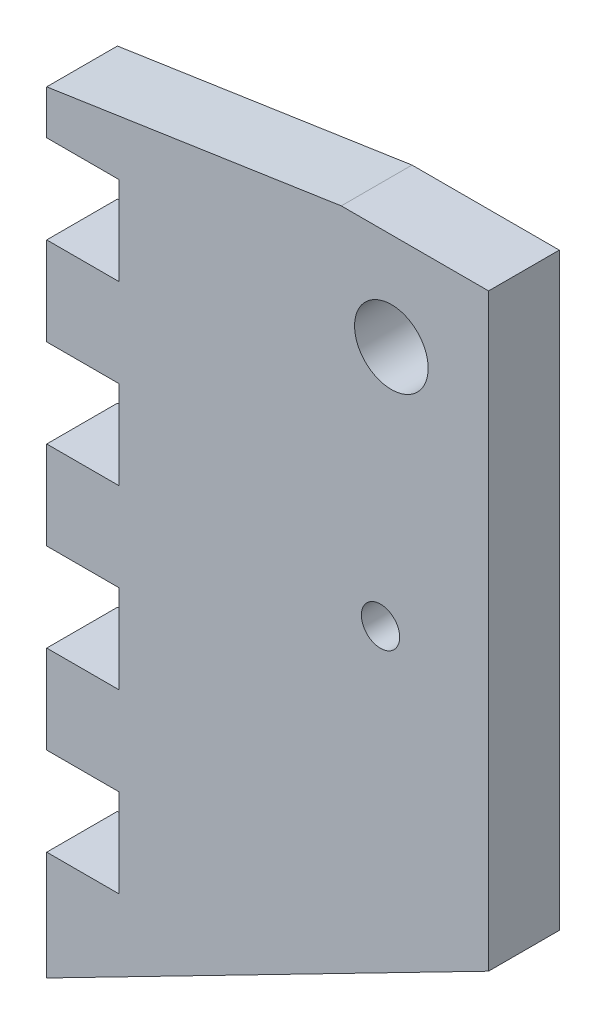
SolidWorks part; units mm, degrees
material "Thornel VCB-20 Carbon Cloth"
ref_plane "Front Plane" through (0, 0, 0) normal (0, 0, 1) x (1, 0, 0)
ref_plane "Top Plane" through (0, 0, 0) normal (0, 1, 0) x (1, 0, 0)
ref_plane "Right Plane" through (0, 0, 0) normal (1, 0, 0) x (0, 0, -1)
sketch "Sketch1" plane through (0, 0, 0) normal (0, 0, 1) x (1, 0, 0)
  line L0 (0, 0) -> (-38.1, 0)
  line L1 (0, 0) -> (0, -50.8)
  line L2 (-38.1, 0) -> (-38.1, -7.62)
  line L3 (-38.1, -7.62) -> (-31.877, -7.62)
  line L4 (-31.877, -7.62) -> (-31.877, -15.24)
  line L5 (-31.877, -15.24) -> (-38.1, -15.24)
  line L6 (-38.1, -45.72) -> (-38.1, -70.358)
  line L7 (-38.1, -15.24) -> (-38.1, -22.86)
  line L8 (-38.1, -22.86) -> (-31.877, -22.86)
  line L9 (-31.877, -22.86) -> (-31.877, -30.48)
  line L10 (-31.877, -30.48) -> (-38.1, -30.48)
  line L11 (-38.1, -30.48) -> (-38.1, -38.1)
  line L12 (-38.1, -38.1) -> (-31.877, -38.1)
  line L13 (-31.877, -38.1) -> (-31.877, -45.72)
  line L14 (-31.877, -45.72) -> (-38.1, -45.72)
  line L15 (-38.1, -70.358) -> (0, -50.8)
  circle A0 centre (-8.382, -8.382) radius 3.175
  dimension "D9" = 6.35
  dimension "D1" = 38.1
  dimension "D2" = 50.8
  dimension "D3" = 7.62
  dimension "D4" = 7.62
  dimension "D6" = 6.223
  dimension "D8" = 70.358
  dimension "D12" = 8.382
  dimension "D13" = 8.382
  dimension "D7" = 3
extrude "Boss-Extrude1" add sketch "Sketch1" along normal blind 6.096 contours L6 L15 L1 L0 L2 L3 L4 L5 L7 L8 L9 L10 L11 L12 L13 L14 A0 region at (-19.2545, -31.1404, 0)
sketch "Sketch2" plane through (0, 0, 0) normal (0, 0, -1) x (-1, 0, 0)
  line L5 (38.1, 0) -> (12.7, 0)
  line L6 (0, 0) -> (38.1, 0) construction
  line L7 (12.7, 0) -> (38.1, -3.81)
  line L8 (38.1, 0) -> (38.1, -7.62) construction
  line L9 (38.1, -3.81) -> (38.1, 0)
  dimension "D1" = 25.4
  dimension "D2" = 3.81
extrude "Cut-Extrude1" cut sketch "Sketch2" against normal blind 8.636
sketch "Sketch4" plane through (0, 0, 6.096) normal (0, 0, 1) x (1, 0, 0)
  line L0 (-38.1, -45.72) -> (-38.1, -53.34)
  line L1 (-38.1, -45.72) -> (-38.1, -70.358) construction
  line L2 (-38.1, -53.34) -> (-31.877, -53.34)
  line L3 (-31.877, -53.34) -> (-31.877, -60.96)
  line L4 (-31.877, -60.96) -> (-38.1, -60.96)
  line L5 (-38.1, -60.96) -> (-38.1, -53.34)
  line M18 (-38.1, -45.72) -> (-38.1, -70.358)
  dimension "D1" = 7.62
  dimension "D2" = 6.223
  dimension "D4" = 7.62
extrude "Cut-Extrude2" cut sketch "Sketch4" against normal through all contours L4 L3 L2 M18 region at (-34.9885, -57.15, 6.096)
sketch "Sketch5" plane through (0, 0, 0) normal (0, 0, -1) x (-1, 0, 0)
  line L0 (8.382, -8.382) -> (9.319, -29.6974) construction
  line L1 (8.382, -8.382) -> (8.382, -39.2411) construction
  circle A0 centre (8.382, -8.382) radius 3.175 construction
  circle A1 centre (9.319, -29.6974) radius 1.651
  dimension "D7" = 3.302
  dimension "D1" = 21.336
  dimension "D2" = 2.517
extrude "Cut-Extrude4" cut sketch "Sketch5" against normal up to surface (6.096 mm away) up to face at (-5.207, -8.382, 6.096)
ref_plane "Plane1" through (0, 0, 0) normal (0, 0, -1) x (-1, 0, 0)
